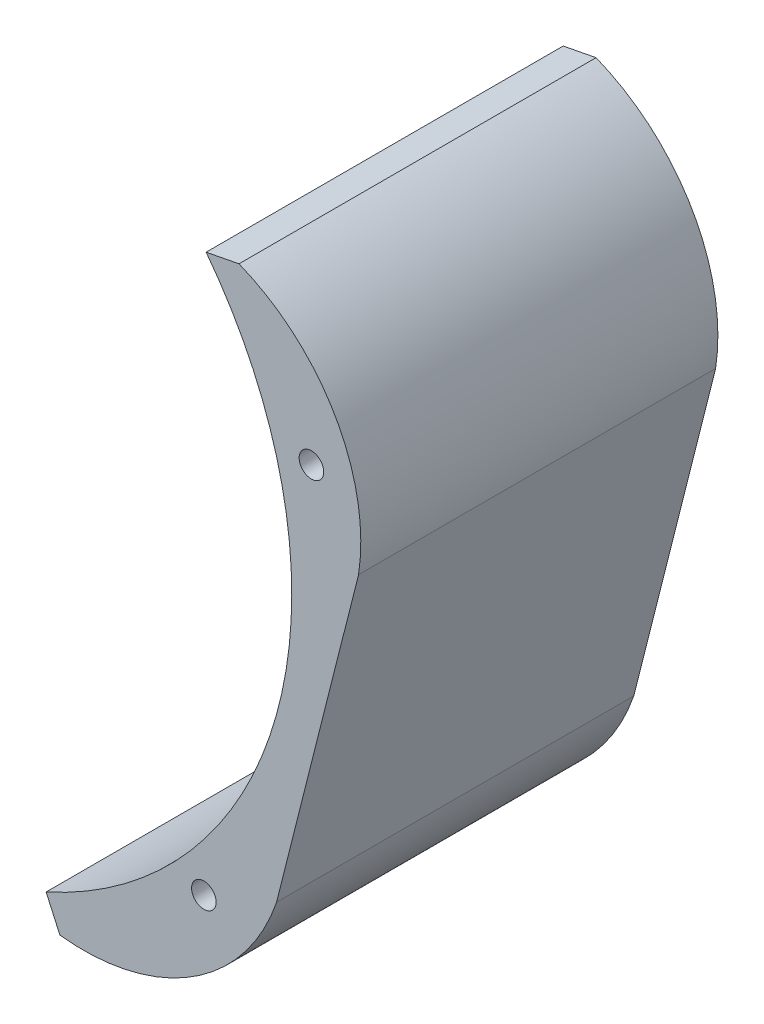
SolidWorks part; units mm, degrees
ref_plane "Płaszczyzna przednia" through (0, 0, 0) normal (0, 0, 1) x (1, 0, 0)
ref_plane "Płaszczyzna górna" through (0, 0, 0) normal (0, 1, 0) x (1, 0, 0)
ref_plane "Płaszczyzna prawa" through (0, 0, 0) normal (1, 0, 0) x (0, 0, -1)
sketch "Szkic1" plane through (0, 0, 0) normal (0, 0, 1) x (1, 0, 0)
  line L0 (2217.0063, 843.7366) -> (2218.2425, 841.0031)
  line L1 (2231.3448, 900.5607) -> (2234.2904, 901.1291)
  line L2 (2231.3448, 900.5607) -> (2217.0063, 843.7366)
  line L3 (2241.3331, 867.8193) -> (2237.6632, 853.2751)
  line L4 (2201.5792, 877.8504) -> (2241.3331, 867.8193) construction
  line L5 (2241.3331, 867.8193) -> (2245.0031, 882.3634)
  arc A0 (2228.0532, 904.3244) -> (2213.2789, 842.2855) centre (2201.5792, 877.8504) cw
  arc A1 (2231.3448, 900.5607) -> (2217.0063, 843.7366) centre (2201.5792, 877.8504) cw
  arc A2 (2234.2904, 901.1291) -> (2245.0031, 882.3634) centre (2227.8459, 885.0096) cw
  arc A3 (2218.2425, 841.0031) -> (2237.6632, 853.2751) centre (2220.3371, 859.1913) ccw
  point P0 (2228.0532, 904.3244)
  point P1 (2213.2789, 842.2855)
  point P7 (2231.3448, 900.5607)
  point P9 (2217.0063, 843.7366)
  dimension "D1" = 5
  dimension "D2" = 4
  dimension "D3" = 3
  dimension "D4" = 3
  dimension "D5" = 15
  dimension "D6" = 15
  dimension "D7" = 41
extrude "Dodanie-wyciągnięcie1" add sketch "Szkic1" along normal blind 32 contours L1 A0 L0 | L4 A1 L0 A3 L3 region at (2231.0926, 851.7286, 0) region at (2240.059, 886.1624, 0)
sketch "Szkic2" plane through (0, 0, 0) normal (0, 0, -1) x (-1, 0, 0)
  circle A0 centre (-2240.7811, 888.768) radius 1.1
  circle A1 centre (-2231.1406, 850.5595) radius 1.1
extrude "Wytnij-wyciągnięcie1" cut sketch "Szkic2" against normal through all
